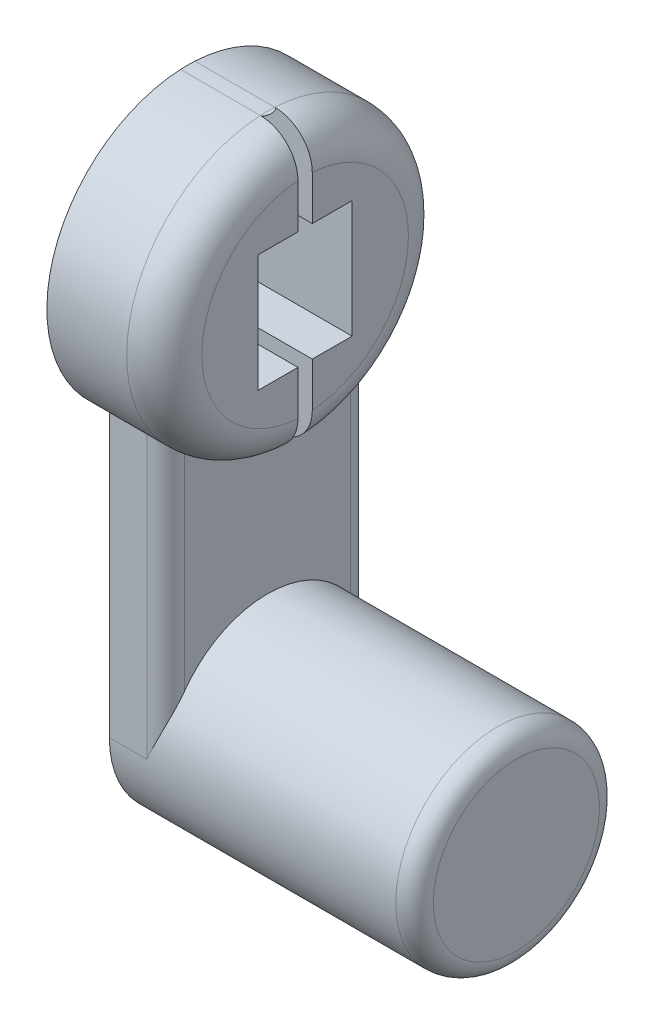
SolidWorks part; units mm, degrees
material "PVC 0.007 Plasticized"
ref_plane "Front Plane" through (0, 0, 0) normal (0, 0, 1) x (1, 0, 0)
ref_plane "Top Plane" through (0, 0, 0) normal (0, 1, 0) x (1, 0, 0)
ref_plane "Right Plane" through (0, 0, 0) normal (1, 0, 0) x (0, 0, -1)
ref_axis "X-Axis" through (-88.99, 0, 0) along (1, 0, 0)
ref_axis "Y-Axis" through (0, 55, 0) along (0, -1, 0)
ref_axis "Z-Axis" through (0, 0, 55) along (0, 0, -1)
sketch "Sketch1" plane through (0, 0, 0) normal (1, 0, 0) x (0, 0, -1)
  circle A0 centre (0, 0) radius 9.525
  dimension "D1" = 19.05
extrude "Boss-Extrude1" add sketch "Sketch1" against normal blind 7.9375
fillet "Fillet1" radius 2.54 1 edges at (0, 0, -9.525)
sketch "Sketch4" plane through (0, 0, 0) normal (1, 0, 0) x (0, 0, -1)
  line L1 (0.4845, -9.5127) -> (-0.4845, -9.5127)
  line L2 (0.4845, -9.5127) -> (0.4845, 9.5127)
  line L3 (0.4845, 9.5127) -> (-0.4845, 9.5127)
  line L4 (-0.4845, -9.5127) -> (-0.4845, 9.5127)
  line L5 (0.4845, -9.5127) -> (-0.4845, 9.5127) construction
  line L6 (0.4845, 9.5127) -> (-0.4845, -9.5127) construction
  circle A0 centre (0, 0) radius 9.525 construction
  point P0 (0, 0)
extrude "Cut-Extrude1" cut sketch "Sketch4" against normal through all
sketch "Sketch6" plane through (0, 0, 0) normal (1, 0, 0) x (0, 0, -1)
  line L1 (-3.175, 3.9688) -> (3.175, 3.9688)
  line L2 (-3.175, 3.9688) -> (-3.175, -3.9688)
  line L3 (-3.175, -3.9688) -> (3.175, -3.9688)
  line L4 (3.175, 3.9688) -> (3.175, -3.9688)
  line L5 (-3.175, 3.9688) -> (3.175, -3.9688) construction
  line L6 (-3.175, -3.9688) -> (3.175, 3.9688) construction
  point P0 (0, 0)
  dimension "D1" = 6.35
  dimension "D2" = 7.9375
extrude "Cut-Extrude2" cut sketch "Sketch6" against normal through all
ref_plane "Plane2" through (-2.54, 0, 0) normal (1, 0, 0) x (0, 0, -1)
sketch "Sketch8" plane through (-2.54, 0, 0) normal (1, 0, 0) x (0, 0, -1)
  line L0 (-6.888, -6.5789) -> (-6.888, -25.6289)
  line L1 (-6.888, -25.6289) -> (6.888, -25.6289)
  line L2 (6.888, -25.6289) -> (6.888, -6.5789)
  arc A0 (-6.888, -6.5789) -> (6.888, -6.5789) centre (0, 0.04) ccw
  arc A1 (-0.4845, 9.5127) -> (-0.4845, -9.5127) centre (0, 0) ccw construction
  arc A2 (0.4845, -9.5127) -> (0.4845, 9.5127) centre (0, 0) ccw construction
  dimension "D1" = 19.05
extrude "Boss-Extrude10" add sketch "Sketch8" against normal up to surface (5.3975 mm away) up to face at (-7.9375, 0, 2.8881)
sketch "Sketch11" plane through (-7.9375, 0, 0) normal (-1, 0, 0) x (0, 0, 1)
  line L0 (-6.888, -25.6289) -> (6.888, -25.6289) construction
  circle A0 centre (0, -25.6289) radius 6.888
extrude "Boss-Extrude12" add sketch "Sketch11" against normal blind 22.225
fillet "Fillet2" radius 1.27 3 edges at (-2.54, -16.1039, -6.888) (-2.54, -16.1039, 6.888) (14.2875, -25.6289, 6.888)
sketch "Sketch12" plane through (-7.9375, 0, 0) normal (-1, 0, 0) x (0, 0, 1)
  line L0 (-6.888, -25.6289) -> (-6.888, -6.5789)
  line L1 (6.888, -25.6289) -> (6.888, -6.5789)
  arc A0 (-6.888, -6.5789) -> (6.888, -6.5789) centre (0, 0) ccw
  arc A1 (-6.888, -25.6289) -> (6.888, -25.6289) centre (0, -25.6289) ccw
extrude "Cut-Extrude3" cut sketch "Sketch12" against normal blind 1.5875
sketch "Sketch13" plane through (-7.9375, 0, 0) normal (-1, 0, 0) x (0, 0, 1)
  line L1 (-3.175, 3.9688) -> (3.175, 3.9688)
  line L2 (-3.175, 3.9688) -> (-3.175, -3.9688)
  line L3 (-3.175, -3.9688) -> (3.175, -3.9688)
  line L4 (3.175, 3.9688) -> (3.175, -3.9688)
extrude "Extrude-Thin1" add sketch "Sketch13" along normal blind 1.27 thin thin type one direction wall 1.016
sketch "Sketch14" plane through (0, 0, 0) normal (1, 0, 0) x (0, 0, -1)
  line L1 (-0.4845, 4.9848) -> (0.4845, 4.9848)
  line L2 (-0.4845, 4.9848) -> (-0.4845, -4.9848)
  line L3 (-0.4845, -4.9848) -> (0.4845, -4.9848)
  line L4 (0.4845, 4.9848) -> (0.4845, -4.9848)
extrude "Cut-Extrude4" cut sketch "Sketch14" against normal through all
